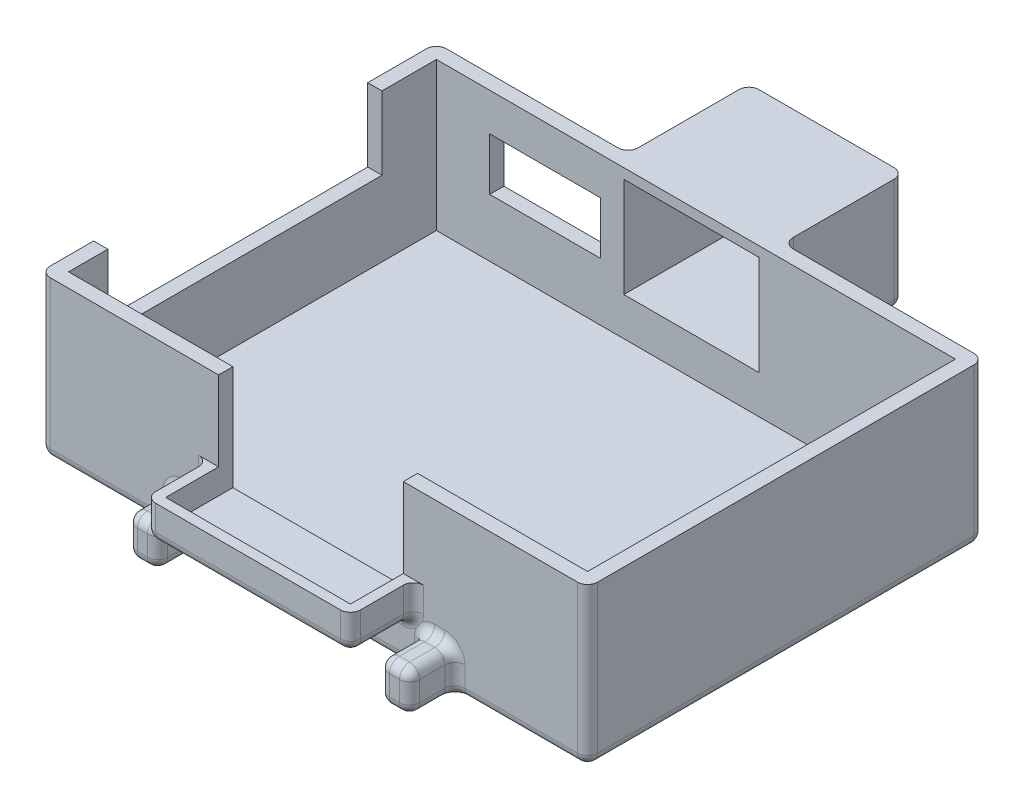
SolidWorks part; units mm, degrees
ref_plane "Front Plane" through (0, 0, 0) normal (0, 0, 1) x (1, 0, 0)
ref_plane "Top Plane" through (0, 0, 0) normal (0, 1, 0) x (1, 0, 0)
ref_plane "Right Plane" through (0, 0, 0) normal (1, 0, 0) x (0, 0, -1)
sketch "Sketch1" plane through (0, 0, 0) normal (0, 1, 0) x (1, 0, 0)
  line L0 (-25.3596, 21.542) -> (-26.7738, 22.9563) construction
  line L1 (-25.3596, 21.542) -> (26.1404, 21.542)
  line L2 (-25.3596, 21.542) -> (-25.3596, -14.958)
  line L3 (-25.3596, -14.958) -> (26.1404, -14.958)
  line L4 (26.1404, 21.542) -> (26.1404, -14.958)
  line L5 (26.1404, -14.958) -> (27.5546, -16.3722) construction
  line L7 (-26.7738, 22.9563) -> (27.5546, 22.9563)
  line L8 (-26.7738, 22.9563) -> (-26.7738, -16.3722)
  line L9 (-26.7738, -16.3722) -> (27.5546, -16.3722)
  line L10 (27.5546, 22.9563) -> (27.5546, -16.3722)
  dimension "D1" = 51.5
  dimension "D2" = 36.5
  dimension "D3" = 2
  dimension "D4" = 2
extrude "Boss-Extrude1" add sketch "Sketch1" along normal blind 1.4 contours L2 L3 L4 L1
extrude "Boss-Extrude2" add sketch "Sketch1<3>" along normal blind 16.1
sketch "Sketch1<3>" plane through (0, 0, 0) normal (0, 1, 0) x (1, 0, 0) same geometry as "Sketch1"
sketch "Sketch4" plane through (27.5546, 0, 0) normal (1, 0, 0) x (0, 0, -1)
  line L0 (22.9563, 16.1) -> (22.9563, 0) construction
  line L1 (-16.3722, 0) -> (22.9563, 0)
  line L2 (-16.3722, 0) -> (-16.3722, 1.4)
  line L3 (-16.3722, 1.4) -> (22.9563, 1.4)
  line L4 (22.9563, 0) -> (22.9563, 1.4)
  dimension "D1" = 1.4
extrude "Cut-Extrude3" cut sketch "Sketch4" against normal blind 60
sketch "Sketch5" plane through (0, 1.4, 0) normal (0, -1, 0) x (1, 0, 0)
  line L0 (-26.7738, 16.3722) -> (27.5546, 16.3722) construction
  line L1 (27.5546, -22.9563) -> (26.1404, -22.9563)
  line L2 (27.5546, -22.9563) -> (27.5546, 16.3722)
  line L3 (27.5546, 16.3722) -> (26.1404, 16.3722)
  line L4 (26.1404, -22.9563) -> (26.1404, 16.3722)
extrude "Boss-Extrude3" add sketch "Sketch5" along normal blind 1
sketch "Sketch6" plane through (26.1404, 0, 0) normal (-1, 0, 0) x (0, 0, 1)
  line L1 (-22.9563, 0.4) -> (16.3722, 0.4)
  line L2 (-22.9563, 0.4) -> (-22.9563, 1.4)
  line L3 (-22.9563, 1.4) -> (16.3722, 1.4)
  line L4 (16.3722, 0.4) -> (16.3722, 1.4)
extrude "Boss-Extrude4" add sketch "Sketch6" along normal up to vertex (52.9142 mm away) up to point (-26.7738, 1.4, -22.9563)
sketch "Sketch7" plane through (-26.7738, 0, 0) normal (-1, 0, 0) x (0, 0, 1)
  line L0 (16.3722, 13.0413) -> (14.9622, 13.0413) construction
  line L1 (16.3722, 16.1) -> (16.3722, 0.4) construction
  line L2 (14.9622, 0.4) -> (14.9622, 1.4) construction
  line L3 (-22.9563, 0.4) -> (16.3722, 0.4) construction
  line L4 (8.9622, 1.4) -> (8.4285, 1.4) construction
  line L5 (14.9622, 1.4) -> (8.9622, 1.4)
  line L6 (14.9622, 1.4) -> (14.9622, 4.4)
  line L7 (14.9622, 4.4) -> (11.0592, 4.4)
  line L8 (8.9622, 1.4) -> (8.9622, 5.85)
  line L9 (8.9622, 5.85) -> (-16.1408, 5.85)
  line L12 (11.0592, 13.85) -> (11.0592, 4.4)
  line L13 (16.3722, 5.85) -> (17.3203, 5.85) construction
  line L15 (11.0592, 13.85) -> (-16.1408, 13.85)
  line L17 (-17.1408, 4.4) -> (-16.1408, 4.4) construction
  line L18 (-16.1408, 5.85) -> (-16.1408, 13.85)
  line L20 (14.9622, 5.85) -> (16.3722, 5.85) construction
  dimension "D1" = 1.41
  dimension "D2" = 1
  dimension "D3" = 3
  dimension "D4" = 1
extrude "Cut-Extrude4" cut sketch "Sketch7" against normal blind 5
sketch "Sketch8" plane through (0, 0, 14.958) normal (0, 0, -1) x (-1, 0, 0)
  line L0 (25.3596, 10.25) -> (9.0596, 10.25) construction
  line L1 (25.3596, 16.1) -> (25.3596, 4.4) construction
  line L2 (21.7738, 1.4) -> (-26.1404, 1.4) construction
  line L4 (9.0596, 10.25) -> (9.0596, 1.4)
  line L5 (9.0596, 1.4) -> (-9.2737, 1.4)
  line L6 (-9.2737, 12.7275) -> (-9.2737, 1.4)
  line L9 (-9.2737, 12.7275) -> (-9.2737, 17.0389)
  line L10 (-9.2737, 17.0389) -> (9.0596, 17.0389)
  line L11 (9.0596, 10.25) -> (9.0596, 17.0389)
  dimension "D1" = 16.3
  dimension "D2" = 18.5
extrude "Cut-Extrude5" cut sketch "Sketch8" against normal blind 5
sketch "Sketch10" plane through (0, 16.1, 0) normal (0, 1, 0) x (1, 0, 0)
  line L0 (-9.0596, -14.958) -> (-9.0596, 21.542) construction
  line L1 (26.1404, 21.542) -> (-25.3596, 21.542) construction
  line L2 (9.2737, -14.958) -> (9.2737, 21.542) construction
  line L3 (27.5546, 22.9563) -> (-26.7738, 22.9563) construction
  line L4 (9.2737, 21.542) -> (-9.0596, 21.542)
  line L5 (9.2737, 21.542) -> (9.2737, 22.9563)
  line L6 (9.2737, 22.9563) -> (-9.0596, 22.9563)
  line L7 (-9.0596, 21.542) -> (-9.0596, 22.9563)
extrude "Cut-Extrude6" cut sketch "Sketch10" against normal blind 12.1
sketch "Sketch11" plane through (0, 0, -22.9563) normal (0, 0, -1) x (-1, 0, 0)
  line L2 (-7.6345, 1.4) -> (-7.6345, 0.4)
  line L3 (-6.6345, 1.4) -> (6.7596, 1.4)
  line L7 (-7.6345, 0.4) -> (7.7596, 0.4)
  line L24 (10.0596, 14.7856) -> (6.7596, 14.7856) construction
  line L25 (26.7738, 0.4) -> (-27.5546, 0.4) construction
  line L27 (6.7596, 13.5) -> (6.7596, 1.4)
  line L30 (7.7596, 0.4) -> (7.7596, 13.5)
  line L31 (6.7596, 13.5) -> (7.7596, 13.5)
  line L32 (-10.2737, 14.5866) -> (-8.2737, 14.5866) construction
  line L34 (-7.6345, 13.5) -> (-6.6345, 13.5)
  line L35 (-7.6345, 13.5) -> (-7.6345, 1.4)
  line L37 (-6.6345, 13.5) -> (-6.6345, 1.4)
  dimension "D2" = 2
  dimension "D4" = 3.3
  dimension "D5" = 1
extrude "Boss-Extrude5" add sketch "Sketch11" along normal blind 12
sketch "Sketch12" plane through (0, 1.4, 0) normal (0, 1, 0) x (1, 0, 0)
  line L1 (6.6345, 34.9563) -> (-6.7596, 34.9563)
  line L3 (6.6345, 33.9563) -> (-6.7596, 33.9563)
  line L5 (-6.7596, 34.9563) -> (-6.7596, 33.9563)
  line L6 (-6.7596, 34.9563) -> (-6.7596, 22.9563) construction
  line L7 (6.6345, 34.9563) -> (6.6345, 33.9563)
sketch "Sketch18" plane through (-26.7738, 0, 0) normal (-1, 0, 0) x (0, 0, 1)
  line L0 (-17.1408, 5.85) -> (-22.9563, 5.85) construction
  line L1 (-22.9563, 16.1) -> (-22.9563, 0.4) construction
sketch "Sketch19" plane through (0, 0, -22.9563) normal (0, 0, -1) x (-1, 0, 0)
  line L0 (26.7738, 5.85) -> (20.0738, 5.85) construction
  line L2 (26.7738, 8.8764) -> (20.0738, 8.8764) construction
  line L3 (26.7738, 16.1) -> (26.7738, 0.4) construction
  line L4 (9.0596, 7.15) -> (9.0596, 9.45)
  line L9 (20.0738, 7.15) -> (20.0738, 9.45)
  line L10 (9.0596, 4) -> (9.0596, 16.1) construction
  line L11 (9.0596, 9.45) -> (9.0596, 10.95)
  line L12 (20.0738, 9.45) -> (20.0738, 10.95)
  line L14 (9.0596, 10.95) -> (9.0596, 12.35)
  line L15 (9.0596, 7.15) -> (20.0738, 7.15)
  line L16 (9.0596, 4) -> (9.0596, 16.1) construction
  line L17 (9.0596, 12.35) -> (20.0738, 12.35)
  line L18 (20.0738, 12.35) -> (20.0738, 10.95)
  dimension "D1" = 6.7
  dimension "D2" = 1.5
  dimension "D3" = 1.4
extrude "Cut-Extrude8" cut sketch "Sketch19" against normal blind 10
extrude "Boss-Extrude6" add sketch "Sketch12" along normal up to vertex (12.1 mm away) up to point (6.6345, 13.5, -34.9563)
sketch "Sketch20" plane through (0, 1.4, 0) normal (0, 1, 0) x (1, 0, 0)
  line L1 (6.6345, 22.9563) -> (9.2737, 22.9563)
  line L2 (6.6345, 22.9563) -> (6.6345, 21.542)
  line L3 (6.6345, 21.542) -> (9.2737, 21.542)
  line L4 (9.2737, 22.9563) -> (9.2737, 21.542)
  line L5 (-9.0596, 22.9563) -> (-6.7596, 22.9563)
  line L6 (-9.0596, 22.9563) -> (-9.0596, 21.542)
  line L7 (-9.0596, 21.542) -> (-6.7596, 21.542)
  line L8 (-6.7596, 22.9563) -> (-6.7596, 21.542)
extrude "Boss-Extrude7" add sketch "Sketch20" along normal up to vertex (12.1 mm away) up to point (6.6345, 13.5, -22.9563)
sketch "Sketch24" plane through (0, 5.85, 0) normal (0, 1, 0) x (1, 0, 0)
  line L1 (-26.7738, 16.1408) -> (-25.3596, 16.1408)
  line L2 (-26.7738, 16.1408) -> (-26.7738, -11.0589)
  line L3 (-26.7738, -11.0589) -> (-25.3596, -11.0589)
  line L4 (-25.3596, 16.1408) -> (-25.3596, -11.0589)
extrude "Cut-Extrude9" cut sketch "Sketch24" along normal blind 15
sketch "Sketch25" plane through (0, 5.85, 0) normal (0, 1, 0) x (1, 0, 0)
  line L1 (-26.7738, 16.1408) -> (-25.3596, 16.1408)
  line L2 (-26.7738, 16.1408) -> (-26.7738, -8.9622)
  line L3 (-26.7738, -8.9622) -> (-25.3596, -8.9622)
  line L4 (-25.3596, 16.1408) -> (-25.3596, -8.9622)
extrude "Boss-Extrude9" add sketch "Sketch25" along normal blind 3
sketch "Sketch26" plane through (0, 13.5, 0) normal (0, 1, 0) x (1, 0, 0)
  line L0 (9.2737, 22.9563) -> (9.2737, 21.542)
  line L1 (9.2737, 21.542) -> (6.6345, 21.542)
  line L2 (6.6345, 21.542) -> (6.6345, 33.9563)
  line L3 (6.6345, 33.9563) -> (-6.7596, 33.9563)
  line L4 (-6.7596, 33.9563) -> (-6.7596, 21.542)
  line L5 (-6.7596, 21.542) -> (-9.0596, 21.542)
  line L6 (-9.0596, 21.542) -> (-9.0596, 22.9563)
  line L7 (-9.0596, 22.9563) -> (-7.7596, 22.9563)
  line L8 (-7.7596, 22.9563) -> (-7.7596, 34.9563)
  line L9 (-7.7596, 34.9563) -> (7.6345, 34.9563)
  line L10 (7.6345, 34.9563) -> (7.6345, 22.9563)
  line L11 (7.6345, 22.9563) -> (9.2737, 22.9563)
extrude "Boss-Extrude10" add sketch "Sketch26" along normal up to vertex (2.6 mm away) up to point (-9.0596, 16.1, -22.9563)
sketch "Sketch27" plane through (0, 4, 0) normal (0, 1, 0) x (1, 0, 0)
  line L1 (6.6345, 22.9563) -> (-6.7596, 22.9563)
  line L2 (6.6345, 22.9563) -> (6.6345, 21.542)
  line L3 (6.6345, 21.542) -> (-6.7596, 21.542)
  line L4 (-6.7596, 22.9563) -> (-6.7596, 21.542)
extrude "Cut-Extrude10" cut sketch "Sketch27" against normal up to vertex (2.6 mm away) up to point (-25.3596, 1.4, -21.542)
sketch "Sketch28" plane through (0, 1.4, 0) normal (0, 1, 0) x (1, 0, 0)
  line L1 (9.2737, -14.958) -> (-9.0596, -14.958)
  line L2 (9.2737, -14.958) -> (9.2737, -16.3722)
  line L3 (9.2737, -16.3722) -> (-9.0596, -16.3722)
  line L4 (-9.0596, -14.958) -> (-9.0596, -16.3722)
extrude "Boss-Extrude11" add sketch "Sketch28" along normal blind 4.3
sketch "Sketch29" plane through (0, 0, 16.3722) normal (0, 0, 1) x (1, 0, 0)
  line L0 (-9.0596, 5.7) -> (-9.0596, 8.2)
  line L3 (-10.0596, 8.2) -> (-10.0596, 4.7)
  line L4 (9.2737, 5.7) -> (9.2737, 8.2)
  line L5 (9.2737, 16.1) -> (9.2737, 5.7) construction
  line L6 (9.2737, 8.2) -> (10.2737, 8.2)
  line L7 (10.2737, 8.2) -> (10.2737, 4.7)
  line L8 (10.2737, 4.7) -> (-10.0596, 4.7)
  line L9 (-9.0596, 5.7) -> (9.2737, 5.7)
  line L12 (9.2737, 16.1) -> (9.2737, 8.2)
  line L13 (-9.0596, 5.7) -> (-9.0596, 16.1) construction
  line L14 (-9.0596, 8.2) -> (-10.0596, 8.2)
  line L20 (9.2737, 5.7) -> (-9.0596, 5.7)
  line L21 (-9.0596, 5.7) -> (-9.0596, 16.1)
  line L22 (-9.0596, 16.1) -> (-26.7738, 16.1)
  line L23 (-26.7738, 16.1) -> (-26.7738, 0.4)
  line L24 (-26.7738, 0.4) -> (27.5546, 0.4)
  line L25 (27.5546, 0.4) -> (27.5546, 16.1)
  line L26 (27.5546, 16.1) -> (9.2737, 16.1)
  line L27 (9.2737, 16.1) -> (9.2737, 5.7)
  line L28 (9.2737, 5.7) -> (-9.0596, 5.7)
  line L30 (-9.0596, 16.1) -> (-26.7738, 16.1)
  line L31 (-26.7738, 16.1) -> (-26.7738, 0.4)
  line L32 (-26.7738, 0.4) -> (27.5546, 0.4)
  line L33 (27.5546, 0.4) -> (27.5546, 16.1)
  line L34 (27.5546, 16.1) -> (9.2737, 16.1)
  line M5 (9.2737, 5.7) -> (-9.0596, 5.7)
  line M6 (-9.0596, 5.7) -> (-9.0596, 16.1)
  line M12 (9.2737, 16.1) -> (9.2737, 5.7)
  dimension "D3" = 3.5
  dimension "D5" = 0
extrude "Boss-Extrude12" add sketch "Sketch29" along normal blind 6.25 contours L14 L3 L8 L7 L6 M6 M12 M5 region at (0.107, 5.5454, 16.3722)
sketch "Sketch30" plane through (0, 5.7, 0) normal (0, 1, 0) x (1, 0, 0)
  line L0 (-9.0596, -14.958) -> (-9.0596, -22.6222) construction
  line L1 (9.2737, -22.6222) -> (-9.0596, -22.6222)
  line L2 (9.2737, -22.6222) -> (9.2737, -21.6222)
  line L3 (9.2737, -21.6222) -> (-9.0596, -21.6222)
  line L4 (-9.0596, -22.6222) -> (-9.0596, -21.6222)
  dimension "D1" = 1
extrude "Boss-Extrude13" add sketch "Sketch30" along normal up to vertex (2.5 mm away) up to point (-9.0596, 8.2, 22.6222)
sketch "Sketch31" plane through (0, 0, 16.3722) normal (0, 0, 1) x (1, 0, 0)
  line L0 (-10.0596, 4.7) -> (10.2737, 4.7) construction
  dimension "D1" = 20.3334
sketch "Sketch32" plane through (6.6345, 0, 0) normal (-1, 0, 0) x (0, 0, 1)
  line L0 (-21.542, 16.1) -> (-21.542, 1.4) construction
  line L1 (-33.9563, 16.1) -> (-21.542, 16.1)
  line L2 (-33.9563, 16.1) -> (-33.9563, 15.1)
  line L3 (-33.9563, 15.1) -> (-21.542, 15.1)
  line L4 (-21.542, 16.1) -> (-21.542, 15.1)
  dimension "D1" = 1
extrude "Boss-Extrude14" add sketch "Sketch32" along normal up to vertex (13.3941 mm away) up to point (-6.7596, 16.1, -21.542)
sketch "Sketch34" plane through (0, 0.4, 0) normal (0, -1, 0) x (1, 0, 0)
  line L1 (7.6345, -22.9563) -> (-7.7596, -22.9563)
  line L2 (7.6345, -22.9563) -> (7.6345, -34.9563)
  line L3 (7.6345, -34.9563) -> (-7.7596, -34.9563)
  line L4 (-7.7596, -22.9563) -> (-7.7596, -34.9563)
extrude "Cut-Extrude11" cut sketch "Sketch34" against normal blind 4.3
sketch "Sketch35" plane through (0, 1.4, 0) normal (0, 1, 0) x (1, 0, 0)
  line L1 (6.6345, 22.9563) -> (-6.7596, 22.9563)
  line L2 (6.6345, 22.9563) -> (6.6345, 21.542)
  line L3 (6.6345, 21.542) -> (-6.7596, 21.542)
  line L4 (-6.7596, 22.9563) -> (-6.7596, 21.542)
extrude "Boss-Extrude15" add sketch "Sketch35" along normal up to vertex (3.3 mm away) up to point (6.6345, 4.7, -22.9563)
sketch "Sketch36" plane through (6.6345, 0, 0) normal (-1, 0, 0) x (0, 0, 1)
  line L0 (-21.542, 15.1) -> (-21.542, 4.7) construction
  line L1 (-33.9563, 4.7) -> (-21.542, 4.7)
  line L2 (-33.9563, 4.7) -> (-33.9563, 5.2)
  line L3 (-33.9563, 5.2) -> (-21.542, 5.2)
  line L4 (-21.542, 4.7) -> (-21.542, 5.2)
  dimension "D1" = 0.5
extrude "Boss-Extrude16" add sketch "Sketch36" along normal up to vertex (13.3941 mm away) up to point (-6.7596, 4.7, -33.9563)
sketch "Sketch37" plane through (0, 0, -22.9563) normal (0, 0, -1) x (-1, 0, 0)
  line L0 (-0.3904, 0.4) -> (-0.3904, 2.4052) construction
  line L1 (26.7738, 0.4) -> (-27.5546, 0.4) construction
  line L2 (-0.3904, 2.4052) -> (-11.3904, 2.4052) construction
  line L3 (-0.3904, 2.4052) -> (10.6096, 2.4052) construction
  line L4 (-16.611, 0.4) -> (-16.611, 4.4) construction
  line L5 (-11.3904, 2.4052) -> (-14.3904, 2.4052) construction
  line L6 (10.6096, 2.4052) -> (13.6096, 2.4052) construction
  line L7 (-14.3904, 4.4) -> (-11.3904, 4.4)
  line L8 (-14.3904, 4.4) -> (-14.3904, 0.4)
  line L9 (-14.3904, 0.4) -> (-11.3904, 0.4)
  line L10 (-11.3904, 4.4) -> (-11.3904, 0.4)
  line L12 (13.6096, 4.4) -> (10.6096, 4.4)
  line L13 (13.6096, 4.4) -> (13.6096, 0.4)
  line L14 (13.6096, 0.4) -> (10.6096, 0.4)
  line L15 (10.6096, 4.4) -> (10.6096, 0.4)
  dimension "D1" = 11
  dimension "D2" = 11
  dimension "D3" = 4
  dimension "D4" = 3
  dimension "D5" = 3
extrude "Boss-Extrude17" add sketch "Sketch37" along normal blind 4.5
sketch "Sketch38" plane through (11.3904, 0, 0) normal (-1, 0, 0) x (0, 0, 1)
  line L0 (-22.9563, 4.4) -> (-27.4563, 0.4) construction
  circle A0 centre (-25.2063, 2.4) radius 0.5
  dimension "D1" = 1
extrude "Cut-Extrude12" cut sketch "Sketch38" against normal blind 2.2
sketch "Sketch39" plane through (-10.6096, 0, 0) normal (1, 0, 0) x (0, 0, -1)
  line L0 (22.9563, 4.4) -> (27.4563, 0.4) construction
  circle A0 centre (25.2063, 2.4) radius 0.5
  dimension "D1" = 1
extrude "Cut-Extrude13" cut sketch "Sketch39" against normal blind 2.2
sketch "Sketch40" plane through (0, 0, 16.3722) normal (0, 0, 1) x (1, 0, 0)
  line L0 (0.3904, 0.4) -> (0.3904, 4.4) construction
  line L1 (27.5546, 0.4) -> (-26.7738, 0.4) construction
  line L2 (0.3904, 4.4) -> (-10.6096, 4.4) construction
  line L3 (0.3904, 4.4) -> (11.3904, 4.4) construction
  line L4 (-10.6096, 4.4) -> (-13.6096, 4.4) construction
  line L5 (11.3904, 4.4) -> (14.3904, 4.4) construction
  line L7 (-13.6096, 4.4) -> (-10.6096, 4.4)
  line L8 (-13.6096, 4.4) -> (-13.6096, 0.4)
  line L9 (-13.6096, 0.4) -> (-10.6096, 0.4)
  line L10 (-10.6096, 4.4) -> (-10.6096, 0.4)
  line L11 (14.3904, 4.4) -> (11.3904, 4.4)
  line L12 (14.3904, 4.4) -> (14.3904, 0.4)
  line L13 (14.3904, 0.4) -> (11.3904, 0.4)
  line L14 (11.3904, 4.4) -> (11.3904, 0.4)
  dimension "D1" = 11
  dimension "D2" = 4
  dimension "D3" = 11
  dimension "D4" = 3
  dimension "D5" = 3
extrude "Boss-Extrude18" add sketch "Sketch40" along normal blind 4.5
sketch "Sketch41" plane through (-10.6096, 0, 0) normal (1, 0, 0) x (0, 0, -1)
  line L0 (-20.8722, 0.4) -> (-16.3722, 4.4) construction
  circle A0 centre (-18.6222, 2.4) radius 0.5
  dimension "D1" = 1
extrude "Cut-Extrude14" cut sketch "Sketch41" against normal blind 2.2
sketch "Sketch42" plane through (11.3904, 0, 0) normal (-1, 0, 0) x (0, 0, 1)
  line L0 (16.3722, 4.4) -> (20.8722, 0.4) construction
  circle A0 centre (18.6222, 2.4) radius 0.5
  dimension "D1" = 1
extrude "Cut-Extrude15" cut sketch "Sketch42" against normal blind 2.2
fillet "Fillet4" radius 1 72 edges at (-10.0596, 6.45, 16.3722) (10.2737, 6.45, 16.3722) (-7.7596, 10.4, -22.9563) (-13.6096, 2.4, -22.9563) (-10.6096, 2.4, -22.9563) (11.3904, 2.4, -22.9563) (14.3904, 2.4, -22.9563) (-10.6096, 2.4, 16.3722) (-13.6096, 2.4, 16.3722) (14.3904, 2.4, 16.3722) (11.3904, 2.4, 16.3722) (-10.0596, 4.7, 19.4972) (0.107, 4.7, 22.6222) (10.2737, 4.7, 19.4972) (0.107, 4.7, 16.3722) (7.6345, 4.7, -28.9563) (-0.0626, 4.7, -34.9563) (-7.7596, 4.7, -28.9563) (-0.0626, 4.7, -22.9563) (11.3904, 2.4, -27.4563) (14.3904, 2.4, -27.4563) (-10.6096, 2.4, -27.4563) (-13.6096, 2.4, -27.4563) (-13.6096, 4.4, -25.2063) (-12.1096, 4.4, -27.4563) (-10.6096, 4.4, -25.2063) (-12.1096, 4.4, -22.9563) (11.3904, 4.4, -25.2063) (12.8904, 4.4, -27.4563) (14.3904, 4.4, -25.2063) (12.8904, 4.4, -22.9563) (-10.6096, 4.4, 18.6222) (-12.1096, 4.4, 20.8722) (-13.6096, 4.4, 18.6222) (-12.1096, 4.4, 16.3722) (14.3904, 4.4, 18.6222) (12.8904, 4.4, 20.8722) (11.3904, 4.4, 18.6222) (12.8904, 4.4, 16.3722) (-26.7738, 0.4, -3.292) (-20.1917, 0.4, 16.3722) (-13.6096, 0.4, 18.6222) (-12.1096, 0.4, 20.8722) (-10.6096, 0.4, 18.6222) (0.3904, 0.4, 16.3722) (11.3904, 0.4, 18.6222) (12.8904, 0.4, 20.8722) (14.3904, 0.4, 18.6222) (20.9725, 0.4, 16.3722) (27.5546, 0.4, -3.292) (20.9725, 0.4, -22.9563) (14.3904, 0.4, -25.2063) (12.8904, 0.4, -27.4563) (11.3904, 0.4, -25.2063) (0.3904, 0.4, -22.9563) (-10.6096, 0.4, -25.2063) (-12.1096, 0.4, -27.4563) (-13.6096, 0.4, -25.2063) (-20.1917, 0.4, -22.9563) (10.2737, 6.45, 22.6222) (-10.0596, 6.45, 22.6222) (27.5546, 8.25, 16.3722) (-26.7738, 8.25, 16.3722) (-26.7738, 8.25, -22.9563) (7.6345, 10.4, -34.9563) (-7.7596, 10.4, -34.9563) (7.6345, 10.4, -22.9563) (27.5546, 8.25, -22.9563) (-10.6096, 2.4, 20.8722) (-13.6096, 2.4, 20.8722) (11.3904, 2.4, 20.8722) (14.3904, 2.4, 20.8722)
